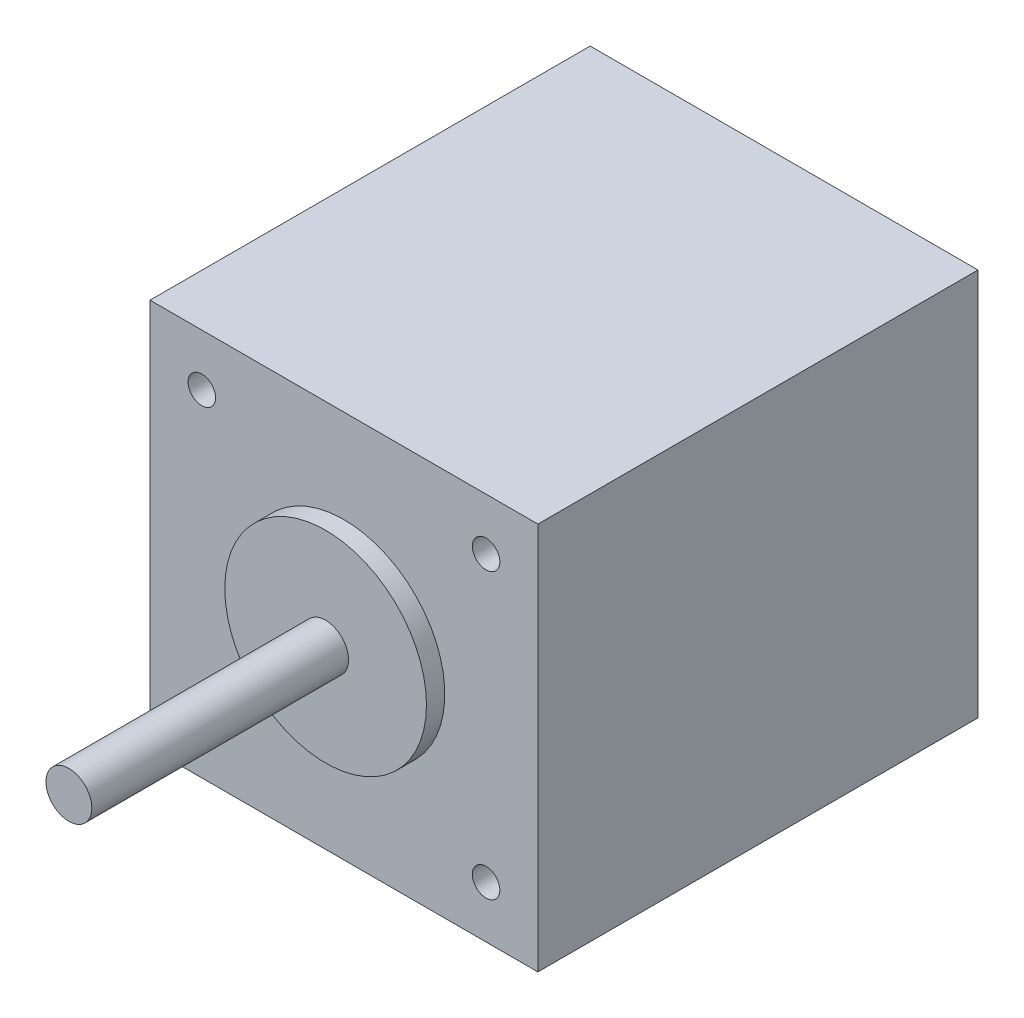
SolidWorks part; units mm, degrees
ref_plane "Спереди" through (0, 0, 0) normal (0, 0, 1) x (1, 0, 0)
ref_plane "Сверху" through (0, 0, 0) normal (0, 1, 0) x (1, 0, 0)
ref_plane "Справа" through (0, 0, 0) normal (1, 0, 0) x (0, 0, -1)
other "Configuration Table"
sketch "Эскиз1" plane through (0, 0, 0) normal (0, 0, 1) x (1, 0, 0)
  line L1 (-21.15, -21.15) -> (21.15, -21.15)
  line L2 (-21.15, -21.15) -> (-21.15, 21.15)
  line L3 (-21.15, 21.15) -> (21.15, 21.15)
  line L4 (21.15, -21.15) -> (21.15, 21.15)
  line L5 (-21.15, -21.15) -> (21.15, 21.15) construction
  line L6 (-21.15, 21.15) -> (21.15, -21.15) construction
  point P0 (0, 0)
  dimension "D1" = 42.3
  dimension "D2" = 42.3
extrude "Корпус" add sketch "Эскиз1" along normal blind 48
sketch "Эскиз2" plane through (0, 0, 0) normal (0, 0, 1) x (1, 0, 0)
  circle A0 centre (0, 0) radius 2.5
extrude "Вал_ПРЕДВ" add sketch "Эскиз2" along normal blind 78
sketch "Эскиз3" plane through (0, 0, 0) normal (0, 0, 1) x (1, 0, 0)
  circle A0 centre (0, 0) radius 11
  dimension "D1" = 22
extrude "Буртик_ПРЕДВ" add sketch "Эскиз3" along normal blind 50
sketch "Эскиз4" plane through (0, 0, 0) normal (0, 0, 1) x (1, 0, 0)
  circle A0 centre (0, 0) radius 8
  dimension "D1" = 16
sketch "Эскиз5" plane through (0, 0, 0) normal (0, 0, 1) x (1, 0, 0)
  circle A0 centre (-15.5, -15.5) radius 1.5
  circle A1 centre (-15.5, 15.5) radius 1.5
  circle A2 centre (15.5, -15.5) radius 1.5
  circle A3 centre (15.5, 15.5) radius 1.5
  dimension "D2" = 3
  dimension "D3" = 3
  dimension "D4" = 3
extrude "Крепеж_М3_ПРЕДВ" cut sketch "Эскиз5" against normal blind 4.5 from offset 48
equation "\"Мотор X ширина корпуса\"= 42.3"
equation "\"Мотор X высота корпуса\"= 42.3"
equation "\"Мотор X длина корпуса\"= 40"
equation "\"Мотор X вылет вала\"= 19.8"
equation "\"Мотор Y ширина корпуса\"= 42.3"
equation "\"Мотор Y высота корпуса\"= 42.3"
equation "\"Мотор Y длина корпуса\"= 48"
equation "\"Мотор Y вылет вала\"= 30"
equation "\"Мотор Z ширина корпуса\"= 42"
equation "\"Мотор Z высота корпуса\"= 42"
equation "\"Мотор Z длина корпуса\"= 40"
equation "\"Мотор Z вылет вала\"= 23"
equation "\"Мотор диаметр вала ПРЕДВ\"= 5"
equation "\"Мотор шаг крепления ПРЕДВ\"= 31"
equation "\"Мотор диаметр отверстий ПРЕДВ\"= 3"
equation "\"Мотор глубина отверстий ПРЕДВ\"= 4.5"
equation "\"Мотор диаметр буртика ПРЕДВ\"= 22"
equation "\"Мотор высота буртика ПРЕДВ\"= 2"
equation "\"Мотор диаметр шкива ПРЕДВ\"= 16"
equation "\"Мотор длина шкива ПРЕДВ\"= 12"
equation "\"Мотор отступ шкива ПРЕДВ\"= 5"
equation "\"Мотор X шаг градусов\"= 1.8"
equation "\"Мотор Y шаг градусов\"= 1.8"
equation "\"Мотор Z шаг градусов\"= 1.8"
equation "\"Мотор Y диаметр ротора\"= 25.78"
equation "\"D1@Эскиз1\" = \"Мотор Y ширина корпуса\""
equation "\"D1@Корпус\" = \"Мотор Y длина корпуса\""
equation "\"D1@Эскиз2\" = \"Мотор диаметр вала ПРЕДВ\""
equation "\"D1@Вал_ПРЕДВ\" = \"Мотор Y длина корпуса\" + \"Мотор Y вылет вала\""
equation "\"D1@Эскиз3\" = \"Мотор диаметр буртика ПРЕДВ\""
equation "\"D1@Буртик_ПРЕДВ\" = \"Мотор Y длина корпуса\" + \"Мотор высота буртика ПРЕДВ\""
equation "\"D1@Эскиз4\" = \"Мотор диаметр шкива ПРЕДВ\""
equation "\"D1@Эскиз5\" = \"Мотор диаметр отверстий ПРЕДВ\""
equation "\"D2@Эскиз5\" = \"Мотор диаметр отверстий ПРЕДВ\""
equation "\"D3@Эскиз5\" = \"Мотор диаметр отверстий ПРЕДВ\""
equation "\"D4@Эскиз5\" = \"Мотор диаметр отверстий ПРЕДВ\""
equation "\"D1@Крепеж_М3_ПРЕДВ\" = \"Мотор глубина отверстий ПРЕДВ\""
equation "\"D19@Крепеж_М3_ПРЕДВ\" = \"Мотор Y длина корпуса\""
equation "\"Ширина груза\"= 420"
equation "\"Глубина груза\"= 490"
equation "\"Высота груза\"= 297"
equation "\"Ширина ячейки\"= \"Ширина груза\" + 10"
equation "\"Глубина ячейки\"= \"Глубина груза\" + 10"
equation "\"Высота ячейки\"= \"Высота груза\" + 10 + 13"
equation "\"Колво ячеек ширина\"= 2"
equation "\"Колво ячеек высота\"= 2"
equation "\"Толщина стенки\"= 10"
equation "\"Крепление дверцы\"= 5"
equation "\"Ширина рейки\"= \"Толщина шестерни\""
equation "\"Высота рейки\"= 20"
equation "\"Высота пола\"= 20"
equation "\"Колво полозьев\"= 5"
equation "\"Отступ рейки\"= 20"
equation "\"Глубина каретки\"= \"Глубина ячейки\" + 30 + \"Мотор Y высота корпуса\" + 20"
equation "\"Отступ шпильки\"= 26"
equation "\"Диаметр шпильки\"= 5"
equation "\"Длинна шпильки\"= ( \"Высота ячейки\" + \"Толщина стенки\" + \"Высота пола\" ) * \"Колво ячеек высота\" + ( \"Толщина стенки\" + \"Отступ рейки\" ) * 2 "
equation "\"Ширина пластины\"= 50  "
equation "\"Высота зона выгрузки\"= \"Высота ячейки\" * 2 + \"Толщина стенки\" * 2"
equation "\"Колво выгрузки\"= 1"
equation "\"Отступ крепления мотора фиксации\" = 30"
equation "\"Ширина ячейки выгрузки\"= \"Ширина ячейки\" + \"Толщина стенки\" + \"Отступ крепления мотора фиксации\"*2"
equation "\"Длинна рейки\"= ( \"Ширина ячейки\" + \"Толщина стенки\" + \"Крепление дверцы\" ) * \"Колво ячеек ширина\" + \"Ширина ячейки выгрузки\" * \"Колво выгрузки\" + \"Толщина стенки\""
equation "\"Толщина шестерни\"= 10"
